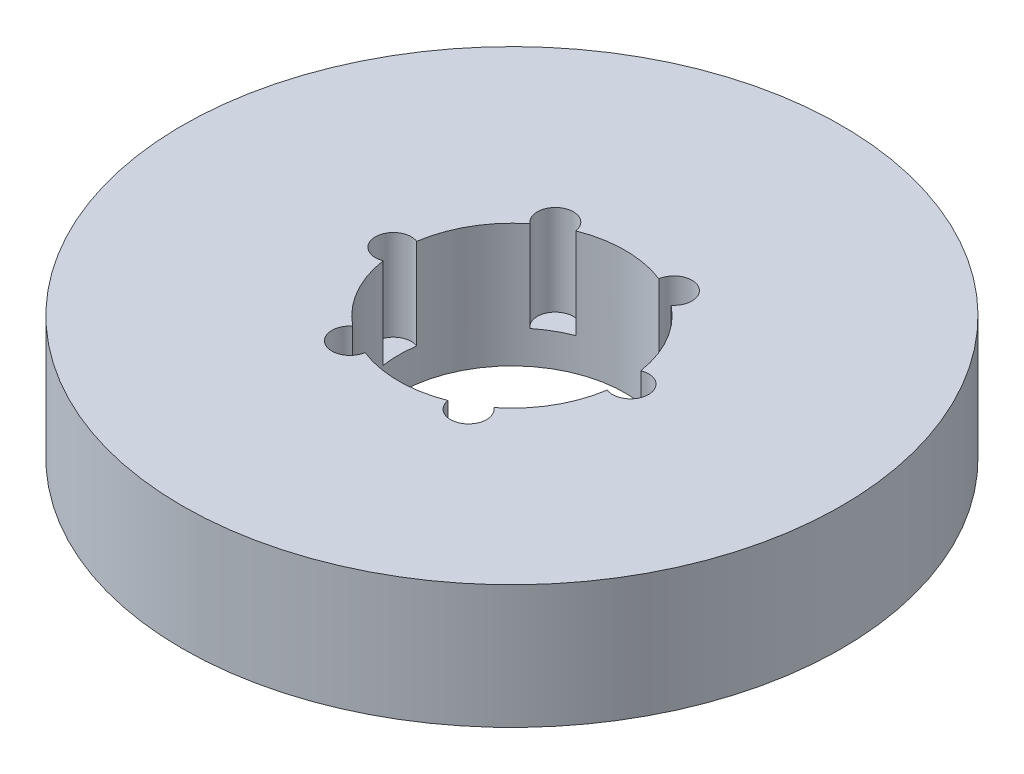
SolidWorks part; units mm, degrees
ref_plane "Front Plane" through (0, 0, 0) normal (0, 0, 1) x (1, 0, 0)
ref_plane "Top Plane" through (0, 0, 0) normal (0, 1, 0) x (1, 0, 0)
ref_plane "Right Plane" through (0, 0, 0) normal (1, 0, 0) x (0, 0, -1)
sketch "Sketch1" plane through (0, 0, 0) normal (0, 1, 0) x (1, 0, 0)
  circle A0 centre (0, 0) radius 80
  dimension "FLANGE_OD" = 160
extrude "Boss-Extrude1" add sketch "Sketch1" along normal blind 30
sketch "Sketch2" plane through (0, 0, 0) normal (0, 1, 0) x (1, 0, 0)
  circle A0 centre (0, 0) radius 27.5
  dimension "BORE_D" = 55
extrude "Cut-Extrude1" cut sketch "Sketch2" along normal through all
sketch "Sketch3" plane through (0, 30, 0) normal (0, 1, 0) x (1, 0, 0)
  circle A0 centre (0, 0) radius 28.7834 construction
  circle A1 centre (-28.7834, 0) radius 4.3767
  dimension "BOLT_D" = 8.7534
  dimension "BOLT_PCD" = 57.5668
extrude "Cut-Extrude2" cut sketch "Sketch3" against normal blind 22.005
pattern_circular "CirPattern1" count 6 over 360 about axis through (0, 0, 0) along (0, 1, 0) of "Cut-Extrude2"
